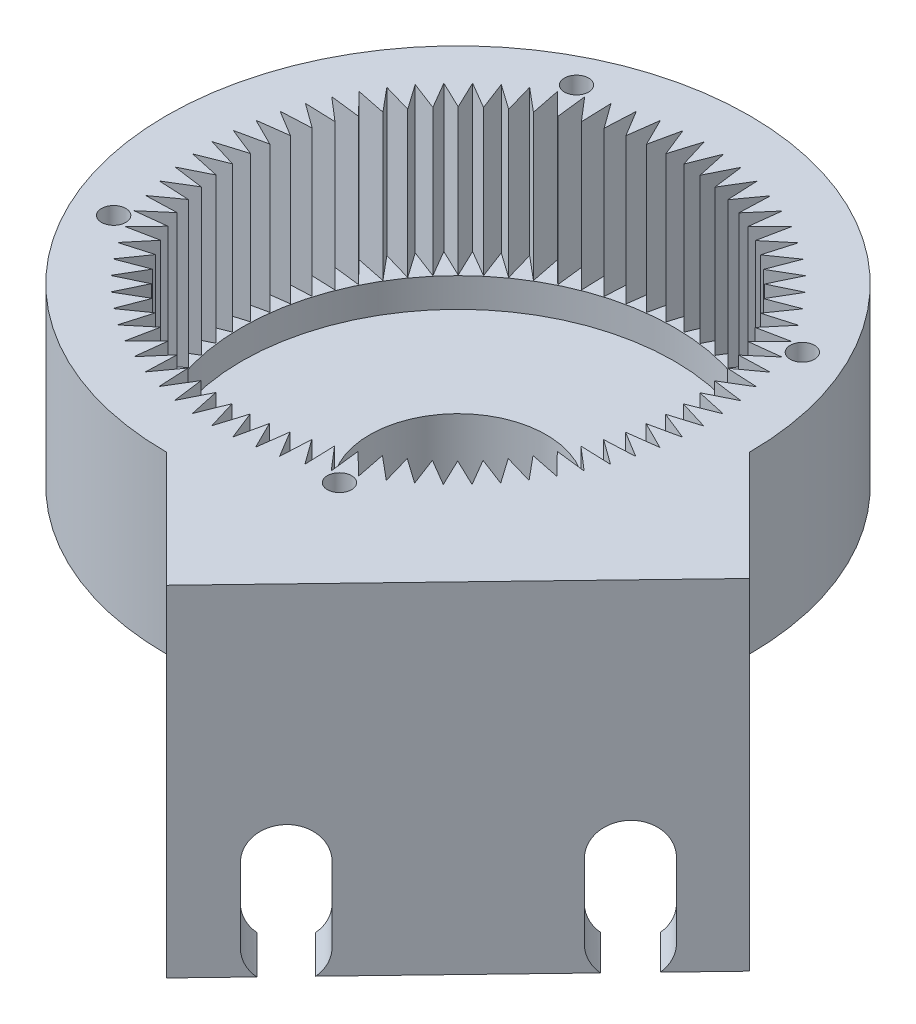
SolidWorks part; units mm, degrees
ref_plane "Front Plane" through (0, 0, 0) normal (0, 0, 1) x (1, 0, 0)
ref_plane "Top Plane" through (0, 0, 0) normal (0, 1, 0) x (1, 0, 0)
ref_plane "Right Plane" through (0, 0, 0) normal (1, 0, 0) x (0, 0, -1)
sketch "Sketch1" plane through (0, 0, 0) normal (0, 1, 0) x (1, 0, 0)
  circle A1 centre (0, 0) radius 23
extrude "Boss-Extrude1" add sketch "Sketch1" against normal blind 2
sketch "Sketch2" plane through (0, 0, 0) normal (0, 1, 0) x (1, 0, 0)
  circle A1 centre (0, 0) radius 22.25
  circle A2 centre (0, 0) radius 30
extrude "Boss-Extrude2" add sketch "Sketch2" along normal blind 18
sketch "Sketch3" plane through (0, 0, 0) normal (0, 1, 0) x (1, 0, 0)
  circle A0 centre (0, 0) radius 9.1
extrude "Cut-Extrude1" cut sketch "Sketch3" against normal blind 10 contours A0
ref_plane "Plane1" through (0, 18, 0) normal (0, 1, 0) x (1, 0, 0)
ref_plane "Plane2" through (0, -2, 0) normal (0, -1, 0) x (-1, 0, 0)
ref_plane "Plane3" through (0, 0, 0) normal (0, -1, 0) x (-1, 0, 0)
ref_axis "Axis1" through (0, -2, 0) along (0, 1, 0)
sketch "Sketch10" plane through (0, 18, 0) normal (0, 1, 0) x (1, 0, 0)
  line L0 (8.1977, -23.9513) -> (8.093, -20.7988)
  line L1 (8.1977, -23.9513) -> (7.2051, -21.0525) construction
  line L2 (8.1977, -23.9513) -> (6.348, -21.3963)
  line L3 (6.192, -24.5467) -> (6.348, -21.3963)
  line L4 (6.192, -24.5467) -> (4.5596, -21.8476)
  line L5 (4.1439, -24.9744) -> (4.5596, -21.8476)
  line L6 (4.1439, -24.9744) -> (2.74, -22.1498)
  line L7 (2.0676, -25.2316) -> (2.74, -22.1498)
  line L8 (2.0676, -25.2316) -> (0.9018, -22.3006)
  line L9 (-0.0229, -25.3164) -> (0.9018, -22.3006)
  line L10 (-0.0229, -25.3164) -> (-0.9427, -22.2991)
  line L11 (-2.1132, -25.2282) -> (-0.9427, -22.2991)
  line L12 (-2.1132, -25.2282) -> (-2.7808, -22.1453)
  line L13 (-4.1892, -24.9678) -> (-2.7808, -22.1453)
  line L14 (-4.1892, -24.9678) -> (-4.5998, -21.8403)
  line L15 (-6.2365, -24.5368) -> (-4.5998, -21.8403)
  line L16 (-6.2365, -24.5368) -> (-6.3875, -21.3861)
  line L17 (-8.2412, -23.9382) -> (-6.3875, -21.3861)
  line L18 (-8.2412, -23.9382) -> (-8.1315, -20.7858)
  line L19 (-10.1897, -23.1761) -> (-8.1315, -20.7858)
  line L20 (-10.1897, -23.1761) -> (-9.8201, -20.0435)
  line L21 (-12.0686, -22.2557) -> (-9.8201, -20.0435)
  line L22 (-12.0686, -22.2557) -> (-11.4415, -19.1644)
  line L23 (-13.865, -21.1833) -> (-11.4415, -19.1644)
  line L24 (-13.865, -21.1833) -> (-12.9848, -18.1543)
  line L25 (-15.5668, -19.9662) -> (-12.9848, -18.1543)
  line L26 (-15.5668, -19.9662) -> (-14.4395, -17.0202)
  line L27 (-17.1623, -18.6128) -> (-14.4395, -17.0202)
  line L28 (-17.1623, -18.6128) -> (-15.7955, -15.7699)
  line L29 (-18.6405, -17.1322) -> (-15.7955, -15.7699)
  line L30 (-18.6405, -17.1322) -> (-17.0436, -14.4119)
  line L31 (-19.9914, -15.5346) -> (-17.0436, -14.4119)
  line L32 (-19.9914, -15.5346) -> (-18.1754, -12.9555)
  line L33 (-21.2058, -13.8309) -> (-18.1754, -12.9555)
  line L34 (-21.2058, -13.8309) -> (-19.1829, -11.4105)
  line L35 (-22.2753, -12.0327) -> (-19.1829, -11.4105)
  line L36 (-22.2753, -12.0327) -> (-20.0595, -9.7877)
  line L37 (-23.1927, -10.1523) -> (-20.0595, -9.7877)
  line L38 (-23.1927, -10.1523) -> (-20.7991, -8.098)
  line L39 (-23.9517, -8.2026) -> (-20.7991, -8.098)
  line L40 (-23.9517, -8.2026) -> (-21.3966, -6.353)
  line L41 (-24.547, -6.1969) -> (-21.3966, -6.353)
  line L42 (-24.547, -6.1969) -> (-21.8479, -4.5646)
  line L43 (-24.9748, -4.1489) -> (-21.8479, -4.5646)
  line L44 (-24.9748, -4.1489) -> (-22.1501, -2.745)
  line L45 (-25.2319, -2.0726) -> (-22.1501, -2.745)
  line L46 (-25.2319, -2.0726) -> (-22.3009, -0.9067)
  line L47 (-25.3167, 0.0179) -> (-22.3009, -0.9067)
  line L48 (-25.3167, 0.0179) -> (-22.2995, 0.9377)
  line L49 (-25.2285, 2.1082) -> (-22.2995, 0.9377)
  line L50 (-25.2285, 2.1082) -> (-22.1457, 2.7758)
  line L51 (-24.9681, 4.1842) -> (-22.1457, 2.7758)
  line L52 (-24.9681, 4.1842) -> (-21.8406, 4.5948)
  line L53 (-24.5371, 6.2315) -> (-21.8406, 4.5948)
  line L54 (-24.5371, 6.2315) -> (-21.3864, 6.3825)
  line L55 (-23.9385, 8.2362) -> (-21.3864, 6.3825)
  line L56 (-23.9385, 8.2362) -> (-20.7861, 8.1265)
  line L57 (-23.1764, 10.1847) -> (-20.7861, 8.1265)
  line L58 (-23.1764, 10.1847) -> (-20.0439, 9.8151)
  line L59 (-22.256, 12.0636) -> (-20.0439, 9.8151)
  line L60 (-22.256, 12.0636) -> (-19.1647, 11.4365)
  line L61 (-21.1836, 13.8601) -> (-19.1647, 11.4365)
  line L62 (-21.1836, 13.8601) -> (-18.1546, 12.9798)
  line L63 (-19.9666, 15.5618) -> (-18.1546, 12.9798)
  line L64 (-19.9666, 15.5618) -> (-17.0206, 14.4345)
  line L65 (-18.6131, 17.1573) -> (-17.0206, 14.4345)
  line L66 (-18.6131, 17.1573) -> (-15.7703, 15.7905)
  line L67 (-17.1325, 18.6355) -> (-15.7703, 15.7905)
  line L68 (-17.1325, 18.6355) -> (-14.4122, 17.0386)
  line L69 (-15.5349, 19.9864) -> (-14.4122, 17.0386)
  line L70 (-15.5349, 19.9864) -> (-12.9558, 18.1704)
  line L71 (-13.8312, 21.2008) -> (-12.9558, 18.1704)
  line L72 (-13.8312, 21.2008) -> (-11.4109, 19.178)
  line L73 (-12.033, 22.2703) -> (-11.4109, 19.178)
  line L74 (-12.033, 22.2703) -> (-9.788, 20.0545)
  line L75 (-10.1527, 23.1877) -> (-9.788, 20.0545)
  line L76 (-10.1527, 23.1877) -> (-8.0983, 20.7941)
  line L77 (-8.203, 23.9467) -> (-8.0983, 20.7941)
  line L78 (-8.203, 23.9467) -> (-6.3533, 21.3916)
  line L79 (-6.1973, 24.542) -> (-6.3533, 21.3916)
  line L80 (-6.1973, 24.542) -> (-4.5649, 21.843)
  line L81 (-4.1493, 24.9698) -> (-4.5649, 21.843)
  line L82 (-4.1493, 24.9698) -> (-2.7454, 22.1451)
  line L83 (-2.0729, 25.2269) -> (-2.7454, 22.1451)
  line L84 (-2.0729, 25.2269) -> (-0.9071, 22.2959)
  line L85 (0.0176, 25.3117) -> (-0.9071, 22.2959)
  line L86 (0.0176, 25.3117) -> (0.9374, 22.2945)
  line L87 (2.1079, 25.2236) -> (0.9374, 22.2945)
  line L88 (2.1079, 25.2236) -> (2.7754, 22.1407)
  line L89 (4.1838, 24.9631) -> (2.7754, 22.1407)
  line L90 (4.1838, 24.9631) -> (4.5945, 21.8356)
  line L91 (6.2312, 24.5321) -> (4.5945, 21.8356)
  line L92 (6.2312, 24.5321) -> (6.3822, 21.3814)
  line L93 (8.2359, 23.9335) -> (6.3822, 21.3814)
  line L94 (8.2359, 23.9335) -> (8.1262, 20.7811)
  line L95 (10.1844, 23.1714) -> (8.1262, 20.7811)
  line L96 (10.1844, 23.1714) -> (9.8147, 20.0389)
  line L97 (12.0633, 22.2511) -> (9.8147, 20.0389)
  line L98 (12.0633, 22.2511) -> (11.4362, 19.1597)
  line L99 (13.8597, 21.1787) -> (11.4362, 19.1597)
  line L100 (13.8597, 21.1787) -> (12.9795, 18.1496)
  line L101 (15.5615, 19.9616) -> (12.9795, 18.1496)
  line L102 (15.5615, 19.9616) -> (14.4341, 17.0156)
  line L103 (17.1569, 18.6081) -> (14.4341, 17.0156)
  line L104 (17.1569, 18.6081) -> (15.7902, 15.7653)
  line L105 (18.6352, 17.1275) -> (15.7902, 15.7653)
  line L106 (18.6352, 17.1275) -> (17.0383, 14.4073)
  line L107 (19.9861, 15.5299) -> (17.0383, 14.4073)
  line L108 (19.9861, 15.5299) -> (18.17, 12.9508)
  line L109 (21.2005, 13.8262) -> (18.17, 12.9508)
  line L110 (21.2005, 13.8262) -> (19.1776, 11.4059)
  line L111 (22.27, 12.028) -> (19.1776, 11.4059)
  line L112 (22.27, 12.028) -> (20.0542, 9.783)
  line L113 (23.1874, 10.1477) -> (20.0542, 9.783)
  line L114 (23.1874, 10.1477) -> (20.7938, 8.0933)
  line L115 (23.9463, 8.198) -> (20.7938, 8.0933)
  line L116 (23.9463, 8.198) -> (21.3913, 6.3483)
  line L117 (24.5417, 6.1923) -> (21.3913, 6.3483)
  line L118 (24.5417, 6.1923) -> (21.8426, 4.5599)
  line L119 (24.9694, 4.1443) -> (21.8426, 4.5599)
  line L120 (24.9694, 4.1443) -> (22.1448, 2.7404)
  line L121 (25.2266, 2.0679) -> (22.1448, 2.7404)
  line L122 (25.2266, 2.0679) -> (22.2956, 0.9021)
  line L123 (25.3114, -0.0226) -> (22.2956, 0.9021)
  line L124 (25.3114, -0.0226) -> (22.2941, -0.9424)
  line L125 (25.2232, -2.1129) -> (22.2941, -0.9424)
  line L126 (25.2232, -2.1129) -> (22.1404, -2.7804)
  line L127 (24.9628, -4.1888) -> (22.1404, -2.7804)
  line L128 (24.9628, -4.1888) -> (21.8353, -4.5995)
  line L129 (24.5318, -6.2362) -> (21.8353, -4.5995)
  line L130 (24.5318, -6.2362) -> (21.3811, -6.3872)
  line L131 (23.9332, -8.2409) -> (21.3811, -6.3872)
  line L132 (23.9332, -8.2409) -> (20.7808, -8.1312)
  line L133 (23.1711, -10.1894) -> (20.7808, -8.1312)
  line L134 (23.1711, -10.1894) -> (20.0385, -9.8197)
  line L135 (22.2507, -12.0683) -> (20.0385, -9.8197)
  line L136 (22.2507, -12.0683) -> (19.1594, -11.4412)
  line L137 (21.1783, -13.8647) -> (19.1594, -11.4412)
  line L138 (21.1783, -13.8647) -> (18.1493, -12.9845)
  line L139 (19.9612, -15.5665) -> (18.1493, -12.9845)
  line L140 (19.9612, -15.5665) -> (17.0153, -14.4391)
  line L141 (18.6078, -17.1619) -> (17.0153, -14.4391)
  line L142 (18.6078, -17.1619) -> (15.7649, -15.7952)
  line L143 (17.1272, -18.6402) -> (15.7649, -15.7952)
  line L144 (17.1272, -18.6402) -> (14.4069, -17.0433)
  line L145 (15.5296, -19.9911) -> (14.4069, -17.0433)
  line L146 (15.5296, -19.9911) -> (12.9505, -18.175)
  line L147 (13.8259, -21.2054) -> (12.9505, -18.175)
  line L148 (13.8259, -21.2054) -> (11.4056, -19.1826)
  line L149 (12.0277, -22.275) -> (11.4056, -19.1826)
  line L150 (12.0277, -22.275) -> (9.7827, -20.0592)
  line L151 (10.1473, -23.1924) -> (9.7827, -20.0592)
  line L152 (10.1473, -23.1924) -> (8.093, -20.7988)
  line L153 (7.2051, -21.0525) -> (8.5216, -24.8974) construction
  point P91 (-0.0027, -0.0023)
  dimension "D1" = 17
extrude "Cut-Extrude8" cut sketch "Sketch10" against normal blind 15
sketch "Sketch5" plane through (0, 18, 0) normal (0, 1, 0) x (1, 0, 0)
  line L0 (0, 0) -> (20.0775, 9.7954) construction
  line L1 (20.0775, 9.7954) -> (26.9622, 13.1544) construction
  circle A1 centre (0, 0) radius 30 construction
  circle A2 centre (23.8167, 11.6197) radius 1.25
  circle A3 centre (11.6197, -23.8167) radius 1.25
  circle A5 centre (-23.8167, -11.6197) radius 1.25
  circle A7 centre (-11.6197, 23.8167) radius 1.25
  point P21 (0, 0)
  dimension "D1" = 4
extrude "Cut-Extrude3" cut sketch "Sketch5" against normal through all
sketch "Sketch8" plane through (0, 0, 0) normal (0, -1, 0) x (-1, 0, 0)
  circle A0 centre (-23.8167, 11.6197) radius 2.5
  circle A1 centre (11.6197, 23.8167) radius 2.5
  circle A2 centre (23.8167, -11.6197) radius 2.5
  circle A3 centre (-11.6197, -23.8167) radius 2.5
  point P11 (0, 0)
  dimension "D1" = 4
extrude "Cut-Extrude5" cut sketch "Sketch8" against normal blind 2
sketch "Sketch11" plane through (0, 18, 0) normal (0, 1, 0) x (1, 0, 0)
  line L0 (0, 0) -> (46.7572, -46.7572) construction
  line L1 (0, -30) -> (11.8636, -41.8636)
  line L2 (0, -30) -> (13.3342, -25.8327)
  line L3 (30, 0) -> (41.2555, -11.2555)
  line L4 (41.2555, -11.2555) -> (11.8636, -41.8636)
  line L5 (13.3342, -25.8327) -> (26.2217, -11.2555)
  line L6 (26.2217, -11.2555) -> (30, 0)
  circle A1 centre (0, 0) radius 30 construction
sketch "Sketch12" plane through (0, 3, 0) normal (0, -1, 0) x (1, 0, 0)
  line L0 (41.2555, 11.2555) -> (11.8636, 41.8636)
  line L1 (11.8636, 41.8636) -> (7.7978, 37.7978)
  line L2 (11.8636, 41.8636) -> (0, 30) construction
  line L3 (7.7978, 37.7978) -> (37.7978, 7.7978)
  line L4 (30, 0) -> (41.2555, 11.2555) construction
  line L5 (37.7978, 7.7978) -> (41.2555, 11.2555)
extrude "Boss-Extrude3" add sketch "Sketch12" along normal blind 20
sketch "Sketch14" plane through (22.7978, 0, 22.7978) normal (-0.7071, 0, -0.7071) x (-0.7071, 0, 0.7071)
  line L0 (-12.5479, -6.784) -> (-12.5479, -14.4481) construction
  line L1 (-9.1969, -6.784) -> (-9.1969, -14.4481)
  line L2 (-15.899, -6.784) -> (-15.899, -14.4481)
  line L3 (12.498, -6.784) -> (12.498, -14.4481) construction
  line L4 (15.8324, -6.784) -> (15.8324, -14.4481)
  line L5 (9.1635, -6.784) -> (9.1635, -14.4481)
  arc A0 (-9.1969, -6.784) -> (-15.899, -6.784) centre (-12.5479, -6.784) ccw
  arc A1 (-15.899, -14.4481) -> (-9.1969, -14.4481) centre (-12.5479, -14.4481) ccw
  arc A2 (15.8324, -6.784) -> (9.1635, -6.784) centre (12.498, -6.784) ccw
  arc A3 (9.1635, -14.4481) -> (15.8324, -14.4481) centre (12.498, -14.4481) ccw
  point P2 (-12.5479, -10.616)
  point P9 (12.498, -10.616)
sketch "Sketch18" plane through (0, 0, 0) normal (0, -1, 0) x (1, 0, 0)
  circle A0 centre (9.881, -35.73) radius 4
  circle A1 centre (35.6359, -9.975) radius 4
extrude "Cut-Extrude13" [suppressed] cut sketch "Sketch18" against normal through all
extrude "Boss-Extrude4" add sketch "Sketch11" against normal blind 17
extrude "Cut-Extrude14" cut sketch "Sketch14" against normal blind 17
sketch "Sketch19" plane through (0, -2, 0) normal (0, -1, 0) x (1, 0, 0)
  circle A0 centre (0, 0) radius 9.1
  circle A1 centre (0, 0) radius 10.9
extrude "Boss-Extrude5" add sketch "Sketch19" along normal blind 16
ref_plane "Plane4" through (0.5563, 0, -0.5563) normal (-0.7071, 0, 0.7071) x (0.7071, 0, 0.7071)
sketch "Sketch20" plane through (0.5563, 0, -0.5563) normal (-0.7071, 0, 0.7071) x (0.7071, 0, 0.7071)
  line L0 (0, -8.9945) -> (0, -13.001) construction
  circle A0 centre (0, -8.9945) radius 0.75
  circle A1 centre (0, -13.001) radius 0.75
extrude "Cut-Extrude15" cut sketch "Sketch20" against normal through all both and the other way through all
